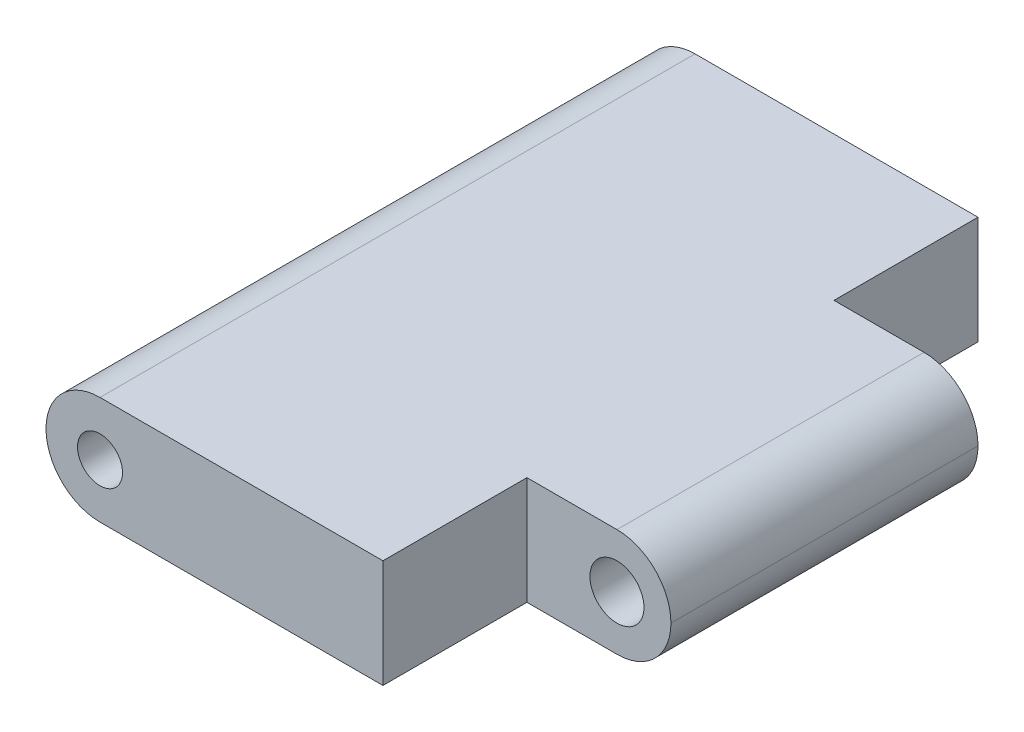
SolidWorks part; units mm, degrees
ref_plane "Front Plane" through (0, 0, 0) normal (0, 0, 1) x (1, 0, 0)
ref_plane "Top Plane" through (0, 0, 0) normal (0, 1, 0) x (1, 0, 0)
ref_plane "Right Plane" through (0, 0, 0) normal (1, 0, 0) x (0, 0, -1)
sketch "Sketch1" plane through (0, 0, 0) normal (0, 1, 0) x (1, 0, 0)
  line L0 (0, 0) -> (0, 16.529)
  line L1 (0, 16.529) -> (13.3591, 16.529)
  line L2 (13.3591, 16.529) -> (13.3591, 0)
  line L3 (13.3591, 0) -> (0, 0)
extrude "Boss-Extrude1" add sketch "Sketch1" along normal blind 3
sketch "Sketch2" plane through (0, 3, 0) normal (0, 1, 0) x (1, 0, 0)
  line L3 (13.3591, 16.529) -> (0, 16.529) construction
  line L6 (9.3591, 16.529) -> (9.3591, 12.529)
  line L7 (9.3591, 12.529) -> (13.3591, 12.529)
  line L8 (13.3591, 0) -> (13.3591, 16.529) construction
  line L9 (13.3591, 12.529) -> (13.3591, 16.529)
  line L10 (13.3591, 16.529) -> (9.3591, 16.529)
  line L13 (0, 0) -> (13.3591, 0) construction
  line L16 (13.3591, 4) -> (9.3591, 4)
  line L17 (9.3591, 4) -> (9.3591, 0)
  line L18 (9.3591, 0) -> (13.3591, 0)
  line L19 (13.3591, 0) -> (13.3591, 4)
  dimension "D1" = 4
  dimension "D2" = 4
  dimension "D3" = 4
  dimension "D4" = 4
extrude "Cut-Extrude1" cut sketch "Sketch2" against normal through all
fillet "Fillet1" radius 1.5 4 edges at (13.3591, 0, -8.2645) (13.3591, 3, -8.2645) (0, 0, -8.2645) (0, 3, -8.2645)
sketch "Sketch5" plane through (0, 0, 0) normal (0, 0, 1) x (1, 0, 0)
  line L0 (1.5, 3) -> (1.5, 0) construction
  line L1 (11.8591, 3) -> (11.8591, 0) construction
  arc A0 (13.3591, 1.5) -> (11.8591, 3) centre (11.8591, 1.5) ccw construction
  circle A1 centre (1.5, 1.5) radius 0.625
  circle A2 centre (11.8591, 1.5) radius 0.75
  dimension "D1" = 1.25
  dimension "D2" = 1.5
extrude "Cut-Extrude3" cut sketch "Sketch5" against normal through all
scale "Scale1" scale about centroid uniform scaling yes scale factor 1.3
